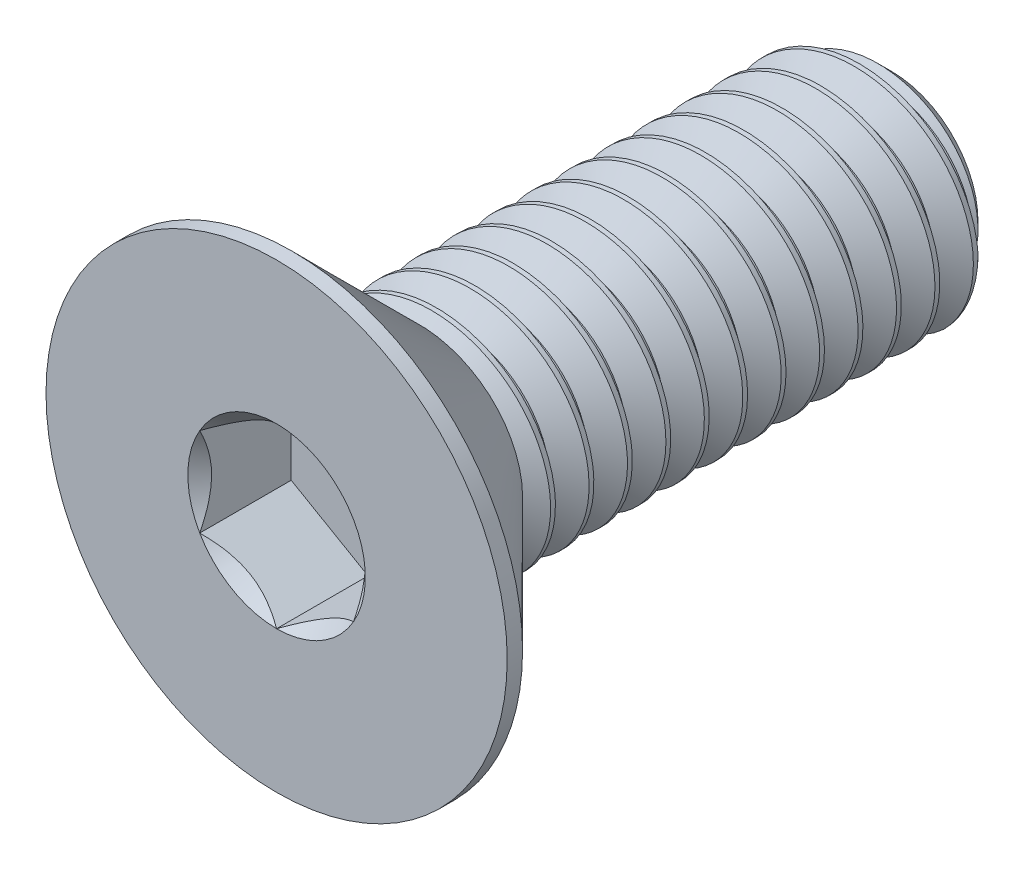
SolidWorks part; units mm, degrees
ref_plane "Front" through (0, 0, 0) normal (0, 0, 1) x (1, 0, 0)
ref_plane "Top" through (0, 0, 0) normal (0, 1, 0) x (1, 0, 0)
ref_plane "Right" through (0, 0, 0) normal (1, 0, 0) x (0, 0, -1)
sketch "Sketch1" plane through (0, 0, 0) normal (1, 0, 0) x (0, 0, -1)
  line L0 (0, 3) -> (0.2, 3) construction
  line L1 (0.2, 3) -> (1.7, 1.5) construction
  line L2 (0, 1.5) -> (8, 1.5)
  line L3 (8, 1.5) -> (8, 0)
  line L4 (8, 0) -> (0, 0)
  line L5 (0, 0) -> (0, 3) construction
  line L6 (0, 3) -> (0, -3) construction
  line L7 (8, 1.5) -> (8, -1.5) construction
  line L8 (0, -3) -> (0.2, -3) construction
  line L9 (0.2, -3) -> (1.7, -1.5) construction
  line L11 (0, 1.5) -> (0, 0)
  line L12 (1.7, 1.5) -> (1.7, 0) construction
  dimension "Head Ht" = 1.7
  dimension "Head Dia" = 6
  dimension "Dia" = 3
  dimension "Lg" = 8
  dimension "Head Angle" = 90
revolve "Revolve1" add sketch "Sketch1" angle 360 mid plane about L4
sketch "Sketch3" plane through (0, 0, -8) normal (0, 0, -1) x (-1, 0, 0)
  circle A0 centre (0, 0) radius 1.5
curve "Helix/Spiral1" pitch 0.5 height 8 radius 1.5 centre (0, 0, -8) axis (0, 0, 1) start towards (0, 1, 0)
sketch "Sketch2" plane through (0, 0, 0) normal (1, 0, 0) x (0, 0, -1)
  line L0 (8, 1.5) -> (8.4375, 1.5)
  line L1 (8.4375, 1.5) -> (8.25, 1.1752)
  line L2 (8.25, 1.1752) -> (8.1875, 1.1752)
  line L3 (8.1875, 1.1752) -> (8, 1.5)
  line L4 (8.0938, 1.3376) -> (8.3438, 1.3376) construction
  dimension "D1" = 60
  dimension "D2" = 0.0625
  dimension "D3" = 0.25
chamfer "Chamfer1" distance 0.375 angle 45 1 edges at (0, 1.5, -8)
sweep "Cut-Sweep1" cut profiles "Sketch2" path "Helix/Spiral1" align with end faces yes
sketch "Sketch7" plane through (0, 0, 0) normal (1, 0, 0) x (0, 0, -1)
  line L0 (0, 3) -> (0.2, 3) construction
  line L1 (0.2, 3) -> (1.7, 1.5) construction
  line L2 (0, 3) -> (0.2, 3)
  line L3 (0.2, 3) -> (1.7, 1.5)
  line L4 (1.7, 1.5) -> (1.7, 0) construction
  line L5 (1.7, 1.5) -> (1.7, 0)
  line L7 (0, 0) -> (0, 3) construction
  line L8 (0, 0) -> (0, 3)
  line L9 (0, 0) -> (1.7, 0)
  line L10 (3.3, 0) -> (-3.3, 0) construction
revolve "Revolve2" add sketch "Sketch7" angle 360 mid plane about L9
ref_plane "Plane1" through (0, 0, -1.7) normal (0, 0, 1) x (1, 0, 0)
sketch "Sketch8" plane through (0, 0, -1.7) normal (0, 0, 1) x (1, 0, 0)
  circle A0 centre (0, 0) radius 1.5
extrude "Boss-Extrude1" add sketch "Sketch8" against normal through all draft 45
sketch "Sketch5" plane through (0, 0, 0) normal (0, 0, 1) x (1, 0, 0)
  line L1 (1, -0.5774) -> (1, 0.5774)
  line L2 (1, 0.5774) -> (0, 1.1547)
  line L3 (0, 1.1547) -> (-1, 0.5774)
  line L4 (-1, 0.5774) -> (-1, -0.5774)
  line L5 (-1, -0.5774) -> (0, -1.1547)
  line L6 (0, -1.1547) -> (1, -0.5774)
  circle A0 centre (0, 0) radius 1 construction
  dimension "Hex" = 2
extrude "Cut-Extrude2" cut sketch "Sketch5" against normal blind 1.19
sketch "Sketch6" plane through (0, 0, 0) normal (0, 0, 1) x (1, 0, 0)
  circle A0 centre (0, 0) radius 1.1547
extrude "Cut-Extrude3" cut sketch "Sketch6" against normal blind 1.19 draft 45
sketch "Sketch9" [suppressed] plane through (0, 0, -5.5) normal (0, 0, 1) x (1, 0, 0)
  circle A1 centre (0, 0) radius 5
  circle A2 centre (0, 0) radius 5
  point P0 (0, 5)
  dimension "D1" = 0
extrude "Boss-Extrude2" [suppressed] add sketch "Sketch9" against normal offset from surface (18.5 mm away) 26 up to face at (0, 1.125, -8)
fillet "Fillet1" [suppressed] radius 0.3
sketch "Sketch10" plane through (0, 0, 0) normal (1, 0, 0) x (0, 0, -1)
  line L0 (8, 1.5) -> (8, -1.5) construction
  point P0 (7.25, -1.5)
  dimension "D1" = 0.75
equation "\"D3@Helix/Spiral1\" = \"Lg@Sketch1\""
equation "\"D2@Sketch2\" = \"D4@Helix/Spiral1\" * .125"
equation "\"D3@Sketch2\" = \"D4@Helix/Spiral1\" * .5"
equation "\"D1@Chamfer1\" = \"D4@Helix/Spiral1\" * .75"
equation "\"D1@Cut-Extrude2\" = \"Head Ht@Sketch1\" * .7"
equation "\"D1@Sketch10\" = \"D4@Helix/Spiral1\" * 1.5"
equation "\"D1@Cut-Extrude3\" = \"D1@Cut-Extrude2\""
equation "\"D1@Fillet1\" = \"Dia@Sketch1\" * .1"
